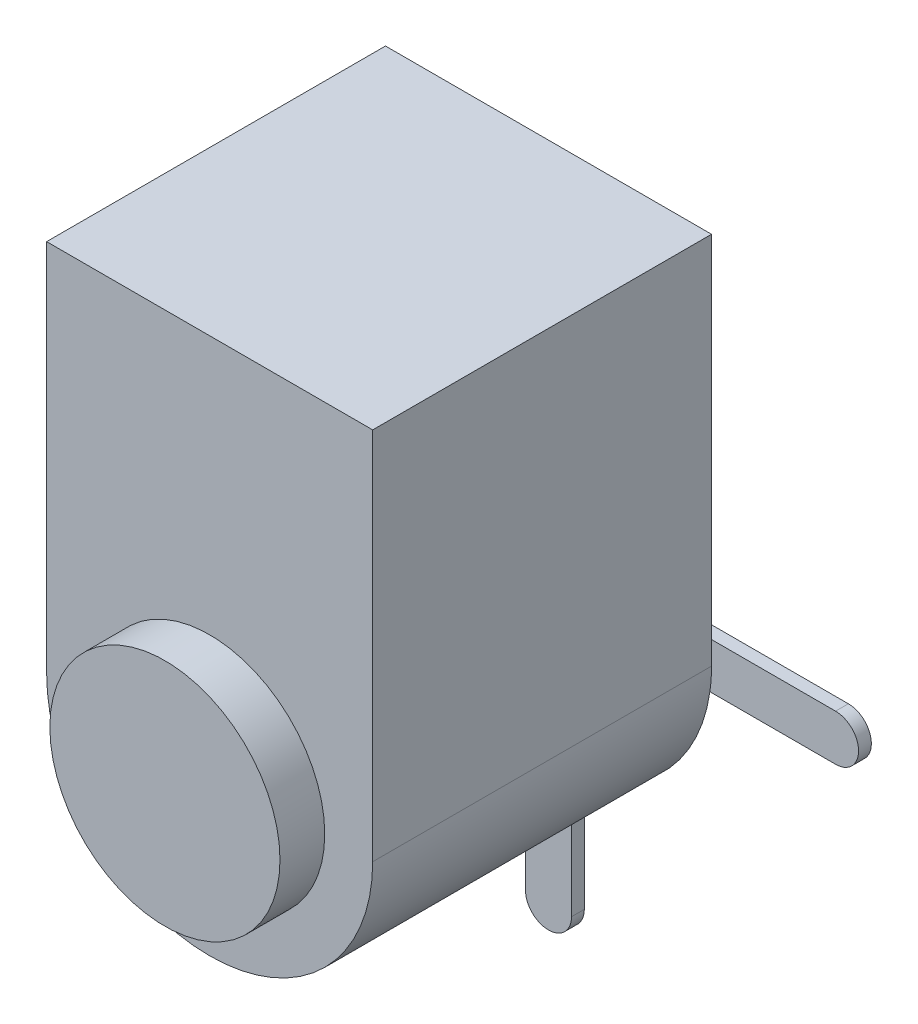
SolidWorks part; units mm, degrees
ref_plane "Front Plane" through (0, 0, 0) normal (0, 0, 1) x (1, 0, 0)
ref_plane "Top Plane" through (0, 0, 0) normal (0, 1, 0) x (1, 0, 0)
ref_plane "Right Plane" through (0, 0, 0) normal (1, 0, 0) x (0, 0, -1)
sketch "Sketch2" plane through (0, 0, 0) normal (0, 0, 1) x (1, 0, 0)
  circle A0 centre (0, 0) radius 18
  dimension "D1" = 36
extrude "Boss-Extrude1" add sketch "Sketch2" along normal blind 60 contours A0
sketch "Sketch3" plane through (0, 0, 0) normal (0, 0, 1) x (1, 0, 0)
  line L1 (-25.5, 0) -> (-25.5, 58.5)
  line L2 (-25.5, 58.5) -> (25.5, 58.5)
  line L3 (25.5, 58.5) -> (25.5, 0)
  arc A0 (-25.5, 0) -> (25.5, 0) centre (0, 0) ccw
  dimension "D1" = 51
extrude "Boss-Extrude2" add sketch "Sketch3" along normal blind 53
sketch "Sketch4" plane through (0, 0, 0) normal (0, 0, 1) x (1, 0, 0)
  line L1 (-3.6, 19.0274) -> (-19.0274, 3.6)
  line L3 (-3.6, -19.0274) -> (-19.0274, -3.6)
  line L4 (3.6, -19.0274) -> (19.0274, -3.6)
  line L5 (3.6, 19.0274) -> (19.0274, 3.6)
  line L6 (3.6, 19.0274) -> (3.6, 44.9)
  line L7 (44.9, 3.6) -> (19.0274, 3.6)
  line L8 (44.9, -3.6) -> (19.0274, -3.6)
  line L9 (-19.0274, 3.6) -> (-44.9, 3.6)
  line L10 (-3.6, 19.0274) -> (-3.6, 44.9)
  line L11 (-19.0274, -3.6) -> (-44.9, -3.6)
  line L14 (3.6, -44.9) -> (3.6, -19.0274)
  line L15 (-3.6, -44.9) -> (-3.6, -19.0274)
  arc A0 (-44.9, 3.6) -> (-44.9, -3.6) centre (-44.9, 0) ccw
  arc A1 (44.9, 3.6) -> (44.9, -3.6) centre (44.9, 0) cw
  arc A2 (-3.6, 44.9) -> (3.6, 44.9) centre (0, 44.9) cw
  arc A3 (-3.6, -44.9) -> (3.6, -44.9) centre (0, -44.9) ccw
  point P0 (-3.6, 19.0274)
  point P2 (3.6, 19.0274)
  point P6 (19.0274, 3.6)
  point P8 (19.0274, -3.6)
  point P9 (3.6, -19.0274)
  point P10 (-3.6, -19.0274)
  point P12 (-19.0274, -3.6)
  point P17 (-19.0274, 3.6)
extrude "Boss-Extrude3" add sketch "Sketch4" against normal blind 2
